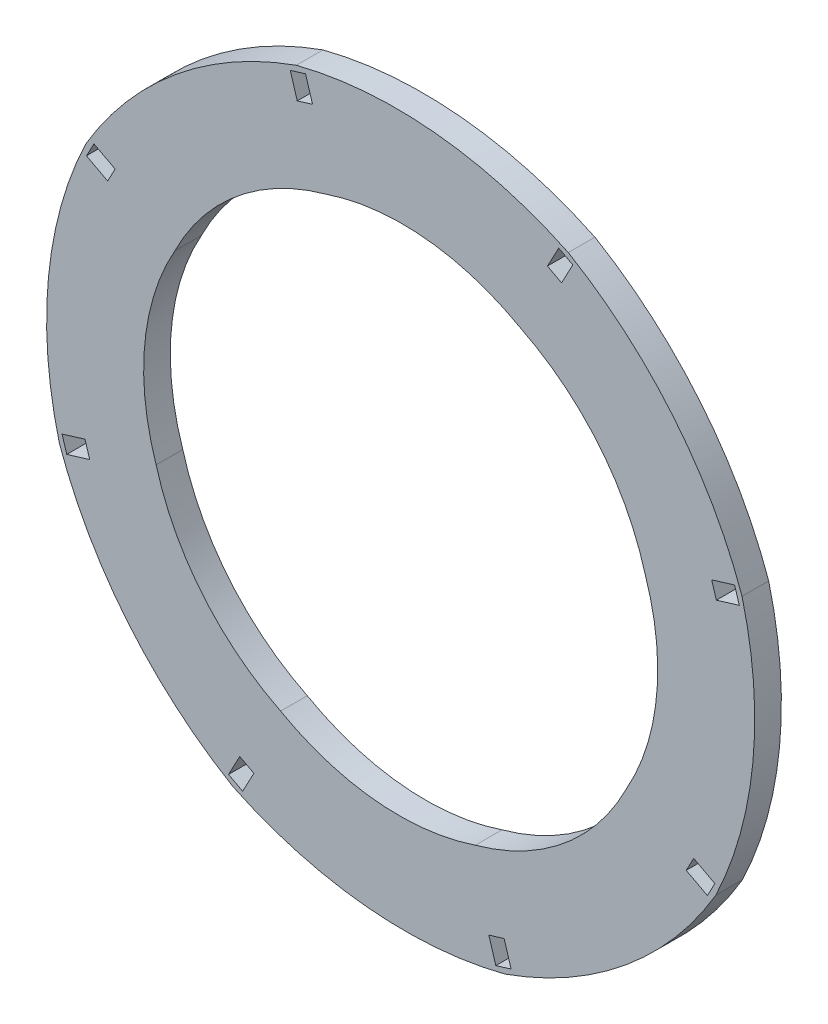
SolidWorks part; units mm, degrees
other "标注1"
sketch "草图3" plane through (-144.6794, 49.1506, 10) normal (-0.0443, 0.015, 0.9989) x (0.9983, -0.0362, 0.0448)
other "标注2"
sketch "草图4" plane through (-144.6794, -217.8569, 10) normal (-0.0889, -0.2563, 0.9625) x (0.9959, -0.04, 0.0813)
ref_plane "前视基准面" through (0, 0, 0) normal (0, 0, 1) x (1, 0, 0)
ref_plane "上视基准面" through (0, 0, 0) normal (0, 1, 0) x (1, 0, 0)
ref_plane "右视基准面" through (0, 0, 0) normal (1, 0, 0) x (0, 0, -1)
sketch "草图1" plane through (0, 0, 0) normal (0, 0, 1) x (1, 0, 0)
  line L0 (215.6616, 312.5399) -> (142.5432, 319.5846) construction
  line L1 (142.5432, 319.5846) -> (129.8661, 295.7457)
  line L3 (226.7697, 276.1996) -> (226.185, 278.1123)
  line L4 (226.185, 278.1123) -> (223.3161, 277.2353)
  line L5 (223.3161, 277.2353) -> (220.6852, 285.8422)
  line L6 (220.6852, 285.8422) -> (223.5542, 286.7192)
  line L7 (223.5542, 286.7192) -> (215.6616, 312.5399)
  line L8 (125.6404, 287.7994) -> (128.2892, 286.3909)
  line L9 (128.2892, 286.3909) -> (132.5149, 294.3372)
  line L10 (132.5149, 294.3372) -> (129.8661, 295.7457)
  line L11 (125.6404, 287.7994) -> (124.7014, 286.0336)
  arc A0 (215.6616, 312.5399) -> (142.5432, 319.5846) centre (186.9822, 397.8481) cw
  arc A1 (226.7697, 276.1996) -> (124.7014, 286.0336) centre (189.2545, 421.4326) cw
  circle A2 centre (214.4723, 254.5061) radius 97 construction
  dimension "D6" = 90
  dimension "D1" = 150
  dimension "D12" = 9
  dimension "D2" = 112.5
  dimension "D3" = 38
  dimension "D4" = 73.457
  dimension "D5" = 38
  dimension "D7" = 2
  dimension "D8" = 3
  dimension "D9" = 9
  dimension "D10" = 2
  dimension "D11" = 3
  dimension "D13" = 112.5
  dimension "D14" = 38
  dimension "D15" = 27
extrude "凸台-拉伸1" add sketch "草图1" along normal blind 10
ref_point "点1"
ref_point "点2"
ref_axis "基准轴1" through (187.6061, 404.3239, 10) along (0, 0, -1)
pattern_circular "阵列(圆周)1" count 8 over 360 about axis through (187.6061, 404.3239, 10) along (0, 0, -1) of "凸台-拉伸1"
